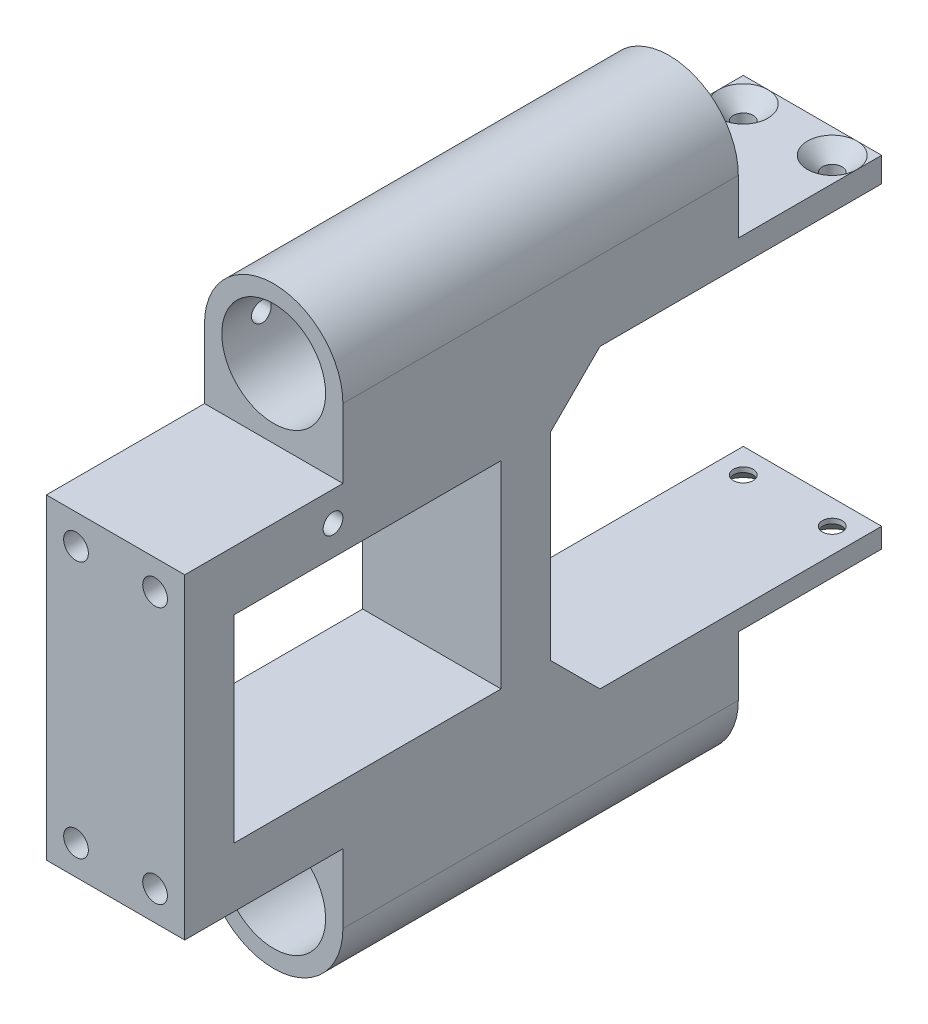
SolidWorks part; units mm, degrees
material "1060 合金"
ref_plane "前视基准面" through (0, 0, 0) normal (0, 0, 1) x (1, 0, 0)
ref_plane "上视基准面" through (0, 0, 0) normal (0, 1, 0) x (1, 0, 0)
ref_plane "右视基准面" through (0, 0, 0) normal (1, 0, 0) x (0, 0, -1)
sketch "草图1" plane through (0, 0, 0) normal (0, 0, 1) x (1, 0, 0)
  line L1 (-14, 64) -> (14, 64)
  line L2 (-14, 64) -> (-14, 0)
  line L3 (-14, 0) -> (14, 0)
  line L4 (14, 64) -> (14, 0)
  point P4 (0, 0)
  dimension "D1" = 28
  dimension "D2" = 64
extrude "凸台-拉伸1" add sketch "草图1" along normal blind 74
sketch "草图2" plane through (0, 0, 74) normal (0, 0, 1) x (1, 0, 0)
  line L0 (14, 64) -> (-14, 64) construction
  line L2 (-14, 0) -> (14, 0) construction
  line L4 (0, 0) -> (0, 64) construction
  circle A0 centre (-8, 58) radius 2.5
  circle A1 centre (8, 58) radius 2.5
  circle A2 centre (-8, 6) radius 2.5
  circle A3 centre (8, 6) radius 2.5
  circle A4 centre (0, -7.5) radius 7.5 construction
  dimension "D1" = 5
  dimension "D6" = 15
  dimension "D2" = 6
  dimension "D3" = 16
  dimension "D4" = 6
  dimension "D7" = 7.5
extrude "切除-拉伸1" cut sketch "草图2" against normal blind 10
sketch "草图3" plane through (0, 0, 0) normal (1, 0, 0) x (0, 0, -1)
  line L0 (-74, 0) -> (-74, 64) construction
  line L1 (-64, 52) -> (-10, 52)
  line L2 (-64, 52) -> (-64, 12)
  line L3 (-64, 12) -> (-10, 12)
  line L4 (-10, 52) -> (-10, 12)
  line L5 (-74, 64) -> (0, 64) construction
  line L6 (0, 0) -> (0, 64) construction
  line L7 (-74, 0) -> (0, 0) construction
  dimension "D1" = 10
  dimension "D2" = 12
  dimension "D3" = 10
  dimension "D4" = 12
extrude "切除-拉伸2" cut sketch "草图3" against normal through all both and the other way through all
ref_plane "基准面1" through (0, 0, -16) normal (0, 0, 1) x (1, 0, 0)
ref_plane "基准面2" through (0, 0, 42) normal (0, 0, 1) x (1, 0, 0)
sketch "草图4" plane through (0, 0, 42) normal (0, 0, -1) x (-1, 0, 0)
  line L0 (-14, 0) -> (-14, 64) construction
  line L5 (14, 32) -> (-14, 32) construction
  line L10 (14, 64) -> (14, 0) construction
  line L12 (-14, 2) -> (14, 2)
  line L13 (-14, 2) -> (-14, -14)
  line L14 (14, 2) -> (14, -14)
  line L15 (14, 0) -> (-14, 0) construction
  line L16 (14, 62) -> (14, 78)
  line L17 (-14, 62) -> (-14, 78)
  line L18 (-14, 62) -> (14, 62)
  circle A1 centre (0, -14) radius 10.5 construction
  circle A2 centre (0, -14) radius 7.5 construction
  arc A3 (-14, -14) -> (14, -14) centre (0, -14) ccw
  circle A4 centre (0, 78) radius 7.5 construction
  circle A5 centre (0, 78) radius 10.5 construction
  arc A6 (-14, 78) -> (14, 78) centre (0, 78) cw
  point P23 (0, 2)
  dimension "D4" = 21
  dimension "D5" = 14
  dimension "D6" = 15
  dimension "D7" = 16
  dimension "D8" = 2
extrude "凸台-拉伸2" add sketch "草图4" along normal blind 80
sketch "草图6" plane through (0, 0, 42) normal (0, 0, -1) x (-1, 0, 0)
  line L0 (14, 32) -> (-14, 32) construction
  line L1 (14, 62) -> (14, 2) construction
  line L2 (-14, 2) -> (-14, 62) construction
  circle A2 centre (0, -14) radius 10.5
  circle A3 centre (0, 78) radius 10.5
  dimension "D1" = 21
extrude "切除-拉伸3" cut sketch "草图6" along normal through all
sketch "草图11" plane through (0, 0, 0) normal (0, 0, -1) x (-1, 0, 0)
  line L0 (14, -14) -> (14, 2) construction
  line L1 (-14, 64) -> (14, 64) construction
  line L3 (-14, 64) -> (14, 64) construction
  line L4 (14, 62) -> (-14, 62)
  line L5 (14, 62) -> (14, 2) construction
  line L6 (-14, 2) -> (-14, 62) construction
  line L7 (-14, 62) -> (-14, 67)
  line L8 (-14, 67) -> (14, 67)
  line L9 (14, 67) -> (14, 62)
  line L14 (-14, 2) -> (14, 2)
  line L15 (-14, 2) -> (-14, -2)
  line L16 (-14, -2) -> (14, -2)
  line L17 (14, 2) -> (14, -2)
  dimension "D1" = 2
  dimension "D2" = 5
  dimension "D3" = 4
extrude "凸台-拉伸5" add sketch "草图11" along normal blind 67
sketch "草图12" plane through (0, 67, 0) normal (0, 1, 0) x (1, 0, 0)
  line L0 (-14, 67) -> (-14, 38) construction
  line L1 (-14, 67) -> (14, 67) construction
  line L2 (14, 67) -> (14, 38) construction
  circle A0 centre (-9, 62) radius 2
  circle A1 centre (9, 62) radius 2
  dimension "D1" = 4
  dimension "D2" = 5
  dimension "D3" = 5
  dimension "D4" = 5
extrude "切除-拉伸8" cut sketch "草图12" against normal through all
chamfer "倒角1" distance 10 angle 45 2 edges at (0, 62, 0) (0, 2, 0)
ref_plane "基准面3" through (0, 0, 2) normal (0, 0, 1) x (1, 0, 0)
sketch "草图13" plane through (0, 0, 2) normal (0, 0, 1) x (1, 0, 0)
  line L0 (-14, 32) -> (14, 32) construction
  line L1 (-14, 64) -> (-14, 0) construction
  line L2 (14, 0) -> (14, 64) construction
  circle A0 centre (0, 78) radius 9.5
  circle A2 centre (0, 78) radius 10.5 construction
  circle A3 centre (0, 78) radius 10.5
  circle A4 centre (0, -14) radius 10.5
  circle A5 centre (0, -14) radius 9.5
  dimension "D1" = 19
extrude "凸台-拉伸6" add sketch "草图13" along normal mid plane 50
sketch "草图14" plane through (0, 0, 0) normal (1, 0, 0) x (0, 0, -1)
  line L0 (-74, 32) -> (44.1527, 32) construction
  line L1 (-74, 0) -> (-74, 64) construction
  line L2 (-42, 92) -> (-42, 78) construction
  line L3 (38, 78) -> (38, 92) construction
  line L4 (-42, 88.5) -> (-42, 67.5) construction
  line L5 (-42, 88.5) -> (-42, 67.5) construction
  circle A0 centre (-34, 78) radius 2
  circle A1 centre (30, 78) radius 2
  circle A2 centre (30, -14) radius 2
  circle A3 centre (-34, -14) radius 2
  point P22 (-42, 78)
  dimension "D1" = 4
  dimension "D2" = 8
  dimension "D3" = 8
extrude "切除-拉伸9" cut sketch "草图14" against normal through all
sketch "草图15" plane through (-14, 0, 0) normal (-1, 0, 0) x (0, 0, 1)
  line L0 (74, 64) -> (42, 64) construction
  line L1 (74, 64) -> (74, 0) construction
  circle A0 centre (44, 58) radius 2
  dimension "D1" = 4
  dimension "D2" = 6
  dimension "D3" = 30
extrude "切除-拉伸10" cut sketch "草图15" against normal through all
chamfer "倒角2" distance 3 angle 45 4 edges at (-9, -2, -60) (9, -2, -60) (-9, 67, -60) (9, 67, -60)
